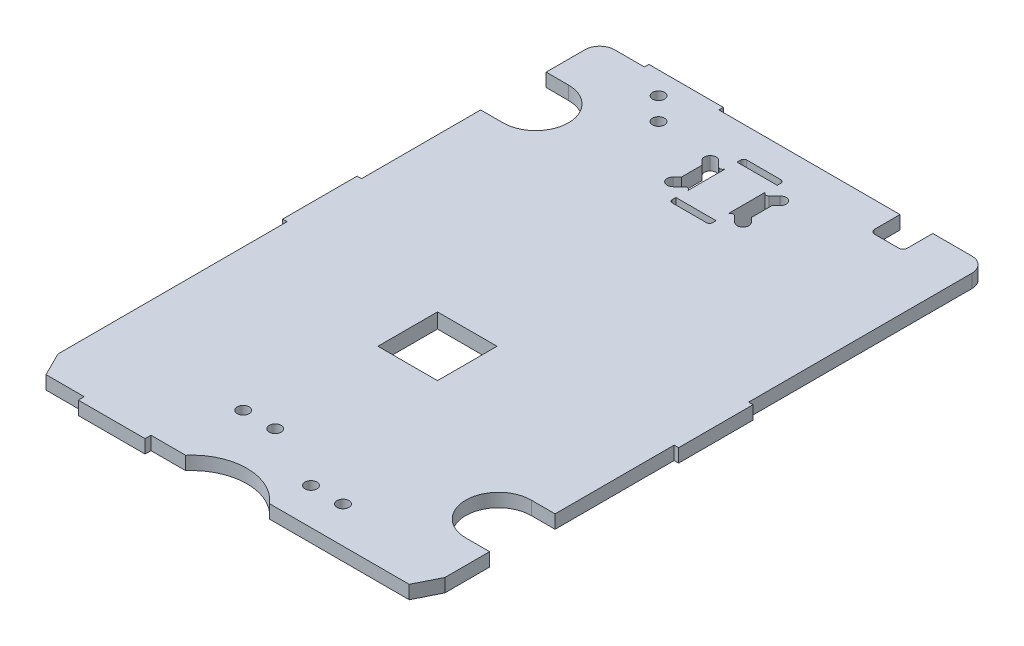
SolidWorks part; units mm, degrees
material "Fibra de vidrio-A"
ref_plane "Alzado" through (0, 0, 0) normal (0, 0, 1) x (1, 0, 0)
ref_plane "Planta" through (0, 0, 0) normal (0, 1, 0) x (1, 0, 0)
ref_plane "Vista lateral" through (0, 0, 0) normal (1, 0, 0) x (0, 0, -1)
sketch "Croquis1" plane through (0, 0, 0) normal (0, 1, 0) x (1, 0, 0)
  line L0 (-12.9456, 11.0109) -> (-11.4456, 11.0109)
  line L1 (-11.4456, 15.4109) -> (-12.9456, 15.4109)
  line L2 (-12.9456, 15.4109) -> (-12.9456, 18.0109)
  line L3 (-11.9456, 19.0109) -> (-9.9456, 19.0109)
  line L4 (-9.9456, 19.0109) -> (7.2294, 19.0109)
  line L5 (7.2294, 19.0109) -> (7.2294, 17.3109)
  line L6 (7.5294, 17.0109) -> (9.1294, 17.0109)
  line L7 (9.4294, 17.3109) -> (9.4294, 19.0109)
  line L8 (9.4294, 19.0109) -> (12.0544, 19.0109)
  line L9 (13.0544, 18.0109) -> (13.0544, -9.9891)
  line L10 (13.0544, -9.9891) -> (11.4544, -9.9891)
  line L11 (11.4544, -14.3891) -> (13.0544, -14.3891)
  line L12 (13.0544, -14.3891) -> (13.0544, -17.3891)
  line L13 (13.0544, -17.3891) -> (12.2544, -18.9891)
  line L14 (12.2544, -18.9891) -> (2.8704, -18.9891)
  line L15 (-2.7616, -18.9891) -> (-12.1456, -18.9891)
  line L16 (-12.1456, -18.9891) -> (-12.9456, -17.3891)
  line L17 (-12.9456, -17.3891) -> (-12.9456, 11.0109)
  line L18 (1.4044, 15.8332) -> (1.4044, 16.8359)
  line L19 (1.2033, 17.0359) -> (-1.0967, 17.0359)
  line L20 (-1.2956, 16.8359) -> (-1.2956, 15.8344)
  line L21 (-1.6362, 15.6922) -> (-2.0128, 16.0687)
  line L22 (-2.5766, 15.5013) -> (-2.2956, 15.2202)
  line L23 (-2.2956, 15.2202) -> (-2.2956, 13.8516)
  line L24 (-2.2956, 13.8516) -> (-2.5802, 13.5669)
  line L25 (-2.0128, 13.0031) -> (-1.6379, 13.3779)
  line L26 (-1.2956, 13.2363) -> (-1.2956, 12.2359)
  line L27 (-1.0945, 12.0359) -> (1.2055, 12.0359)
  line L28 (1.4044, 12.2359) -> (1.4044, 13.2385)
  line L29 (1.7467, 13.3779) -> (2.1216, 13.0031)
  line L30 (2.689, 13.5669) -> (2.4044, 13.8516)
  line L31 (2.4044, 13.8516) -> (2.4044, 15.2202)
  line L32 (2.4044, 15.2202) -> (2.6855, 15.5013)
  line L33 (2.1216, 16.0686) -> (1.7466, 15.6938)
  arc A0 (-11.4456, 11.0109) -> (-9.2456, 13.2109) centre (-11.4456, 13.2109) ccw
  arc A1 (-9.2456, 13.2109) -> (-11.4456, 15.4109) centre (-11.4456, 13.2109) ccw
  arc A2 (-12.9456, 18.0109) -> (-11.9456, 19.0109) centre (-11.9456, 18.0109) cw
  arc A3 (7.2294, 17.3109) -> (7.5294, 17.0109) centre (7.5294, 17.3109) ccw
  arc A4 (9.1294, 17.0109) -> (9.4294, 17.3109) centre (9.1294, 17.3109) ccw
  arc A5 (12.0544, 19.0109) -> (13.0544, 18.0109) centre (12.0544, 18.0109) cw
  arc A6 (11.4544, -9.9891) -> (9.2544, -12.1891) centre (11.4544, -12.1891) ccw
  arc A7 (9.2544, -12.1891) -> (11.4544, -14.3891) centre (11.4544, -12.1891) ccw
  arc A8 (-2.7616, -18.9891) -> (2.8704, -18.9891) centre (0.0544, -21.389) cw
  arc A9 (1.4044, 16.8359) -> (1.2033, 17.0359) centre (1.2044, 16.8359) ccw
  arc A10 (-1.0967, 17.0359) -> (-1.2956, 16.8359) centre (-1.0967, 16.837) ccw
  arc A11 (-1.2956, 15.8344) -> (-1.6362, 15.6922) centre (-1.4956, 15.8344) cw
  arc A12 (-2.0128, 16.0687) -> (-2.5802, 16.0687) centre (-2.2965, 15.7849) ccw
  arc A13 (-2.5802, 16.0687) -> (-2.5766, 15.5013) centre (-2.2984, 15.7867) ccw
  arc A14 (-2.5802, 13.5669) -> (-2.5766, 13.0031) centre (-2.3, 13.2867) ccw
  arc A15 (-2.5766, 13.0031) -> (-2.0128, 13.0031) centre (-2.2947, 13.2921) ccw
  arc A16 (-1.6379, 13.3779) -> (-1.2956, 13.2363) centre (-1.4962, 13.2361) cw
  arc A17 (-1.2956, 12.2359) -> (-1.0945, 12.0359) centre (-1.0956, 12.2359) ccw
  arc A18 (1.2055, 12.0359) -> (1.4044, 12.2359) centre (1.2055, 12.2348) ccw
  arc A19 (1.4044, 13.2385) -> (1.7467, 13.3779) centre (1.6039, 13.2385) cw
  arc A20 (2.1216, 13.0031) -> (2.6854, 13.0031) centre (2.4035, 13.2851) ccw
  arc A21 (2.6854, 13.0031) -> (2.689, 13.5669) centre (2.4017, 13.2868) ccw
  arc A22 (2.6855, 15.5013) -> (2.6883, 16.068) centre (2.4006, 15.7861) ccw
  arc A23 (2.6883, 16.068) -> (2.1216, 16.0686) centre (2.4047, 15.79) ccw
  arc A24 (1.7466, 15.6938) -> (1.5289, 15.6492) centre (1.6039, 15.8365) cw
  arc A25 (1.5289, 15.6492) -> (1.4044, 15.8332) centre (1.6026, 15.8332) cw
  circle A26 centre (-6.2956, 16.3109) radius 0.4
  circle A27 centre (-7.7956, 17.8109) radius 0.4
  circle A28 centre (5.3544, -16.5391) radius 0.4
  circle A29 centre (3.2044, -16.5391) radius 0.4
  circle A30 centre (-1.2956, -14.4391) radius 0.4
  circle A31 centre (-3.4456, -14.4391) radius 0.4
  dimension "D1" = 38
extrude "Saliente-Extruir1" add sketch "Croquis1" along normal blind 0.9
sketch "Croquis8" plane through (0, 0, 0) normal (0, -1, 0) x (1, 0, 0)
  line L0 (13.0544, 9.9891) -> (13.0544, -18.0109) construction
  line L1 (-4.4456, 7.9891) -> (2.5544, 7.9891)
  line L2 (-4.9456, 7.4891) -> (-4.9456, 0.4891)
  line L3 (-4.4456, -0.0109) -> (2.5544, -0.0109)
  line L4 (3.0544, 7.4891) -> (3.0544, 0.4891)
  line L5 (-12.1456, 18.9891) -> (-2.7616, 18.9891) construction
  arc A0 (2.5544, -0.0109) -> (3.0544, 0.4891) centre (2.5544, 0.4891) ccw
  arc A1 (-4.9456, 0.4891) -> (-4.4456, -0.0109) centre (-4.4456, 0.4891) ccw
  arc A2 (-4.4456, 7.9891) -> (-4.9456, 7.4891) centre (-4.4456, 7.4891) ccw
  arc A3 (2.5544, 7.9891) -> (3.0544, 7.4891) centre (2.5544, 7.4891) cw
  point P6 (3.0544, -0.0109)
  point P11 (-4.9456, 7.9891)
  point P14 (3.0544, 7.9891)
  dimension "D3" = 0.5
  dimension "D1" = 8
  dimension "D2" = 8
  dimension "D4" = 10
  dimension "D5" = 11
extrude "Saliente-Extruir2" add sketch "Croquis8" along normal blind 0.1
sketch "Croquis9" plane through (0, -0.1, 0) normal (0, -1, 0) x (1, 0, 0)
  line L0 (2.5544, 7.9891) -> (-4.4456, 7.9891) construction
  line L1 (-2.6456, 6.1891) -> (1.3544, 6.1891)
  line L2 (-2.6456, 6.1891) -> (-2.6456, 2.1891)
  line L3 (-2.6456, 2.1891) -> (1.3544, 2.1891)
  line L4 (1.3544, 6.1891) -> (1.3544, 2.1891)
  line L5 (-4.9456, 7.4891) -> (-4.9456, 0.4891) construction
  dimension "D1" = 4
  dimension "D2" = 4
  dimension "D3" = 1.8
  dimension "D4" = 2.3
extrude "Cortar-Extruir1" cut sketch "Croquis9" against normal through all
sketch "Croquis11" plane through (0, 0, 0) normal (0, -1, 0) x (1, 0, 0)
  line L0 (-9.4456, -7.1568) -> (-7.7456, -7.1568)
  line L1 (-10.5756, -2.1709) -> (-5.9456, -2.1709)
  line L2 (-10.5756, -2.1709) -> (-10.5756, -5.3709)
  line L3 (-10.5756, -5.3709) -> (-5.9456, -5.3709)
  line L4 (-5.9456, -2.1709) -> (-5.9456, -5.3709)
  line L5 (8.2544, 0.6891) -> (9.0544, 0.6891)
  line L6 (8.2544, 0.6891) -> (8.2544, -0.9109)
  line L7 (8.2544, -0.9109) -> (9.0544, -0.9109)
  line L8 (9.0544, 0.6891) -> (9.0544, -0.9109)
  line L9 (7.5544, -4.3109) -> (10.5544, -4.3109)
  line L10 (7.5544, -4.3109) -> (7.5544, -7.0109)
  line L11 (7.5544, -7.0109) -> (10.5544, -7.0109)
  line L12 (10.5544, -4.3109) -> (10.5544, -7.0109)
  line L13 (9.5544, -0.4109) -> (10.0544, -0.4109)
  line L14 (9.5544, -0.4109) -> (9.5544, -1.4109)
  line L15 (9.5544, -1.4109) -> (10.0544, -1.4109)
  line L16 (10.0544, -0.4109) -> (10.0544, -1.4109)
  line L17 (10.7544, 6.9891) -> (11.7544, 6.9891)
  line L18 (10.7544, 6.9891) -> (10.7544, 6.4891)
  line L19 (10.7544, 6.4891) -> (11.7544, 6.4891)
  line L20 (11.7544, 6.9891) -> (11.7544, 6.4891)
  line L21 (10.7544, 6.1891) -> (11.7544, 6.1891)
  line L22 (10.7544, 6.1891) -> (10.7544, 5.6891)
  line L23 (10.7544, 5.6891) -> (11.7544, 5.6891)
  line L24 (11.7544, 6.1891) -> (11.7544, 5.6891)
  line L25 (8.5544, -2.3109) -> (9.5544, -2.3109)
  line L26 (8.5544, -2.3109) -> (8.5544, -2.8109)
  line L27 (8.5544, -2.8109) -> (9.5544, -2.8109)
  line L28 (9.5544, -2.3109) -> (9.5544, -2.8109)
  line L29 (11.1544, -2.0799) -> (11.6544, -2.0799)
  line L30 (11.1544, -2.0799) -> (11.1544, -3.0799)
  line L31 (11.1544, -3.0799) -> (11.6544, -3.0799)
  line L32 (11.6544, -2.0799) -> (11.6544, -3.0799)
  line L33 (11.1544, -5.5575) -> (11.6544, -5.5575)
  line L34 (11.1544, -5.5575) -> (11.1544, -6.5575)
  line L35 (11.1544, -6.5575) -> (11.6544, -6.5575)
  line L36 (11.6544, -5.5575) -> (11.6544, -6.5575)
  line L37 (7.7544, -8.5109) -> (8.7544, -8.5109)
  line L38 (7.7544, -8.5109) -> (7.7544, -9.0109)
  line L39 (7.7544, -9.0109) -> (8.7544, -9.0109)
  line L40 (8.7544, -8.5109) -> (8.7544, -9.0109)
  line L41 (10.6544, -8.5109) -> (11.6544, -8.5109)
  line L42 (10.6544, -8.5109) -> (10.6544, -9.0109)
  line L43 (10.6544, -9.0109) -> (11.6544, -9.0109)
  line L44 (11.6544, -8.5109) -> (11.6544, -9.0109)
  line L45 (-11.4456, -7.1709) -> (-9.7456, -7.1709)
  line L46 (-11.4456, -7.1709) -> (-11.4456, -9.2709)
  line L47 (-11.4456, -9.2709) -> (-9.7456, -9.2709)
  line L48 (-9.7456, -7.1709) -> (-9.7456, -9.2709)
  line L57 (-10.6456, -5.9701) -> (-9.6456, -5.9701)
  line L58 (-10.6456, -5.9701) -> (-10.6456, -6.4701)
  line L59 (-10.6456, -6.4701) -> (-9.6456, -6.4701)
  line L60 (-9.6456, -5.9701) -> (-9.6456, -6.4701)
  line L61 (-8.5456, -16.3109) -> (-6.4456, -16.3109)
  line L62 (-8.5456, -16.3109) -> (-8.5456, -17.5109)
  line L63 (-8.5456, -17.5109) -> (-6.4456, -17.5109)
  line L64 (-6.4456, -16.3109) -> (-6.4456, -17.5109)
  line L65 (-1.2956, -12.4759) -> (1.4044, -12.4759)
  line L66 (-1.2956, -12.4759) -> (-1.2956, -16.5859)
  line L67 (-1.2956, -16.5859) -> (1.4044, -16.5859)
  line L68 (1.4044, -12.4759) -> (1.4044, -16.5859)
  line L69 (-9.4456, -7.1568) -> (-9.4456, -9.2568)
  line L70 (-9.4456, -9.2568) -> (-7.7456, -9.2568)
  line L71 (-7.7456, -7.1568) -> (-7.7456, -9.2568)
  line L72 (-7.4456, -7.1551) -> (-5.8368, -7.1551)
  line L73 (-7.4456, -7.1551) -> (-7.4456, -9.2551)
  line L74 (-7.4456, -9.2551) -> (-5.8368, -9.2551)
  line L75 (-5.8368, -7.1551) -> (-5.8368, -9.2551)
  line L76 (-12.9456, -11.0109) -> (-12.9456, 17.3891) construction
  line L77 (-12.1456, 18.9891) -> (-2.7616, 18.9891) construction
  line L78 (7.2294, -19.0109) -> (-11.9456, -19.0109) construction
  line L79 (-12.9456, -18.0109) -> (-12.9456, -15.4109) construction
  line L80 (-1.2956, -13.2363) -> (-1.2956, -12.2359) construction
  line L81 (1.2033, -17.0359) -> (-1.0967, -17.0359) construction
  line L84 (13.0544, 9.9891) -> (13.0544, -18.0109) construction
  line L86 (2.8704, 18.9891) -> (12.2544, 18.9891) construction
  line L87 (12.0544, -19.0109) -> (9.4294, -19.0109) construction
  point P84 (10.6544, -8.7609)
  dimension "D1" = 0.5
  dimension "D2" = 1
  dimension "D3" = 0.5
  dimension "D4" = 1
  dimension "D5" = 0.5
  dimension "D6" = 1
  dimension "D7" = 0.5
  dimension "D8" = 1
  dimension "D9" = 0.5
  dimension "D10" = 1
  dimension "D11" = 0.5
  dimension "D12" = 1
  dimension "D13" = 1
  dimension "D14" = 0.5
  dimension "D15" = 0.5
  dimension "D16" = 1
  dimension "D17" = 3
  dimension "D18" = 2.7
  dimension "D19" = 1.6
  dimension "D20" = 0.8
  dimension "D21" = 1
  dimension "D22" = 0.5
  dimension "D23" = 4.63
  dimension "D24" = 3.2
  dimension "D25" = 2.1
  dimension "D26" = 1.7
  dimension "D27" = 1.5
  dimension "D28" = 5.2
  dimension "D29" = 0.3
  dimension "D30" = 0.3
  dimension "D31" = 28.26
  dimension "D32" = 24.36
  dimension "D33" = 7
  dimension "D34" = 2.3
  dimension "D35" = 2.1
  dimension "D36" = 1.2
  dimension "D37" = 1.5
  dimension "D38" = 4.4
  dimension "D39" = 4.11
  dimension "D40" = 2.7
  dimension "D41" = 0.45
  dimension "D42" = 1.3
  dimension "D43" = 1.3
  dimension "D44" = 12
  dimension "D45" = 0.3
  dimension "D46" = 18.3
  dimension "D47" = 4
  dimension "D48" = 3
  dimension "D49" = 19.4
  dimension "D50" = 21.3
  dimension "D51" = 3.5
  dimension "D52" = 1.4
  dimension "D53" = 1.4
  dimension "D54" = 2.5
  dimension "D55" = 1.4
  dimension "D56" = 1.9
  dimension "D57" = 14.7
  dimension "D58" = 10.5
  dimension "D59" = 10.5
extrude "Saliente-Extruir3" add sketch "Croquis11" along normal blind 0.5
sketch "Croquis12" plane through (0, -0.5, 0) normal (0, -1, 0) x (1, 0, 0)
  line L2 (-8.2606, -2.1709) -> (-8.2606, -5.3709) construction
  circle A4 centre (-8.2606, -3.7709) radius 1.6
extrude "Saliente-Extruir5" add sketch "Croquis12" along normal blind 1.5
sketch "Croquis13" plane through (0, -2, 0) normal (0, -1, 0) x (1, 0, 0)
  line L0 (-5.9456, -2.1709) -> (-8.2606, -2.1709) construction
  line L1 (-10.0606, -2.1709) -> (-6.4422, -2.1709)
  line L2 (-10.0606, -2.1709) -> (-10.0606, -5.3709)
  line L3 (-10.0606, -5.3709) -> (-6.4422, -5.3709)
  line L4 (-6.4422, -2.1709) -> (-6.4422, -5.3709)
  line L5 (-10.5756, -5.3709) -> (-5.9456, -5.3709) construction
extrude "Saliente-Extruir6" add sketch "Croquis13" along normal blind 0.5
sketch "Croquis15" plane through (0, -0.5, 0) normal (0, -1, 0) x (1, 0, 0)
  line L4 (7.5544, -4.3109) -> (7.5544, -7.0109)
  line L5 (7.5544, -7.0109) -> (10.5544, -7.0109)
  line L6 (10.5544, -7.0109) -> (10.5544, -4.3109)
  line L7 (10.5544, -4.3109) -> (7.5544, -4.3109)
  line L8 (7.5544, -4.3109) -> (7.5544, -7.0109)
  line L9 (7.5544, -7.0109) -> (10.5544, -7.0109)
  line L10 (10.5544, -7.0109) -> (10.5544, -4.3109)
  line L11 (10.5544, -4.3109) -> (7.5544, -4.3109)
  dimension "D1" = 0
extrude "Saliente-Extruir7" add sketch "Croquis15" along normal blind 0.4
sketch "Croquis16" plane through (0, -0.5, 0) normal (0, -1, 0) x (1, 0, 0)
  line L4 (-1.2956, -12.4759) -> (-1.2956, -16.5859)
  line L5 (-1.2956, -16.5859) -> (1.4044, -16.5859)
  line L6 (1.4044, -16.5859) -> (1.4044, -12.4759)
  line L7 (1.4044, -12.4759) -> (-1.2956, -12.4759)
  line L8 (-1.2956, -12.4759) -> (-1.2956, -16.5859)
  line L9 (-1.2956, -16.5859) -> (1.4044, -16.5859)
  line L10 (1.4044, -16.5859) -> (1.4044, -12.4759)
  line L11 (1.4044, -12.4759) -> (-1.2956, -12.4759)
  dimension "D1" = 0
extrude "Saliente-Extruir8" add sketch "Croquis16" along normal blind 2
fillet "Redondeo1" radius 1.5 2 edges at (1.4044, -2.5, -14.5309) (-1.2956, -2.5, -14.5309)
sketch "Croquis17" plane through (0, 0, -16.5859) normal (0, 0, -1) x (-1, 0, 0)
  line L0 (1.0956, -1) -> (1.0956, -0.2)
  line L1 (1.0956, -0.2) -> (-1.2044, -0.2)
  line L2 (-1.2044, -0.2) -> (-1.2044, -1)
  line L3 (1.2956, -1) -> (1.2956, 0)
  line L4 (1.2956, 0) -> (-1.4044, 0)
  line L5 (-1.4044, 0) -> (-1.4044, -1)
  line L12 (1.2956, 0) -> (-1.4044, 0) construction
  line L13 (1.2956, -1) -> (1.2956, 0) construction
  line L14 (-1.4044, 0) -> (-1.4044, -1) construction
  arc A0 (-1.2044, -1) -> (-0.0544, -2.2913) centre (0.0956, -1) ccw
  arc A1 (-0.0544, -2.2913) -> (1.0956, -1) centre (-0.2044, -1) ccw
  arc A2 (-1.4044, -1) -> (-0.0544, -2.4925) centre (0.0956, -1) ccw
  arc A3 (-0.0544, -2.4925) -> (1.2956, -1) centre (-0.2044, -1) ccw
  arc A4 (-1.4044, -1) -> (-0.0544, -2.4925) centre (0.0956, -1) ccw
  arc A8 (-0.0544, -2.4925) -> (1.2956, -1) centre (-0.2044, -1) ccw construction
  dimension "D1" = 0
  dimension "D2" = 0.2
extrude "Cortar-Extruir3" cut sketch "Croquis17" against normal up to surface (4.11 mm away) contours A0 A1 L0 L1 L2 up to face at (0.0544, -1.0025, -12.4759)
sketch "Croquis21" plane through (0, 0, 0) normal (0, 1, 0) x (1, 0, 0)
  line L4 (-1.2956, 16.5859) -> (-1.2956, 12.4759)
  line L5 (-1.2956, 12.4759) -> (1.4044, 12.4759)
  line L6 (1.4044, 12.4759) -> (1.4044, 16.5859)
  line L7 (1.4044, 16.5859) -> (-1.2956, 16.5859)
  line L8 (-1.2956, 16.5859) -> (-1.2956, 12.4759)
  line L9 (-1.2956, 12.4759) -> (1.4044, 12.4759)
  line L10 (1.4044, 12.4759) -> (1.4044, 16.5859)
  line L11 (1.4044, 16.5859) -> (-1.2956, 16.5859)
  dimension "D1" = 0
extrude "Saliente-Extruir10" add sketch "Croquis21" along normal up to vertex (0.9 mm away) up to point (-1.0945, 0.9, -12.0359)
sketch "Croquis22" plane through (0, 0.9, 0) normal (0, 1, 0) x (1, 0, 0)
  line L0 (-12.9456, 11.0109) -> (-12.9456, -17.3891) construction
  line L1 (-12.9456, -1.9891) -> (-13.2456, -1.9891)
  line L2 (-12.9456, -1.9891) -> (-12.9456, 3.0109)
  line L3 (-12.9456, 3.0109) -> (-13.2456, 3.0109)
  line L4 (-13.2456, -1.9891) -> (-13.2456, 3.0109)
  line L5 (-12.1456, -18.9891) -> (-2.7616, -18.9891) construction
  line L6 (-9.5802, -18.9891) -> (-5.0942, -18.9891)
  line L7 (-9.5802, -18.9891) -> (-9.5802, -19.3856)
  line L8 (-9.5802, -19.3856) -> (-5.0942, -19.3856)
  line L9 (-5.0942, -18.9891) -> (-5.0942, -19.3856)
  line L10 (7.2294, 19.0109) -> (-11.9456, 19.0109) construction
  line L11 (-9.9456, 19.0109) -> (-4.9456, 19.0109)
  line L12 (-9.9456, 19.0109) -> (-9.9456, 19.3109)
  line L13 (-9.9456, 19.3109) -> (-4.9456, 19.3109)
  line L14 (-4.9456, 19.0109) -> (-4.9456, 19.3109)
  line L15 (13.0544, -9.9891) -> (13.0544, 18.0109) construction
  line L16 (13.0544, 3.0109) -> (13.3544, 3.0109)
  line L17 (13.0544, 3.0109) -> (13.0544, -1.9891)
  line L18 (13.0544, -1.9891) -> (13.3544, -1.9891)
  line L19 (13.3544, 3.0109) -> (13.3544, -1.9891)
  line L20 (-12.9456, 18.0109) -> (-12.9456, 15.4109) construction
  line L21 (12.0544, 19.0109) -> (9.4294, 19.0109) construction
  line L22 (2.8704, -18.9891) -> (12.2544, -18.9891) construction
  point P26 (-4.9456, 19.1609)
  dimension "D1" = 3
  dimension "D2" = 18
  dimension "D3" = 0.3
  dimension "D4" = 0.3
  dimension "D5" = 17
  dimension "D6" = 16
  dimension "D7" = 16
  dimension "D8" = 17
  dimension "D9" = 0.3
extrude "Saliente-Extruir11" add sketch "Croquis22" against normal up to surface (0.9 mm away) up to face at (-7.3804, 0, -17.0911)
